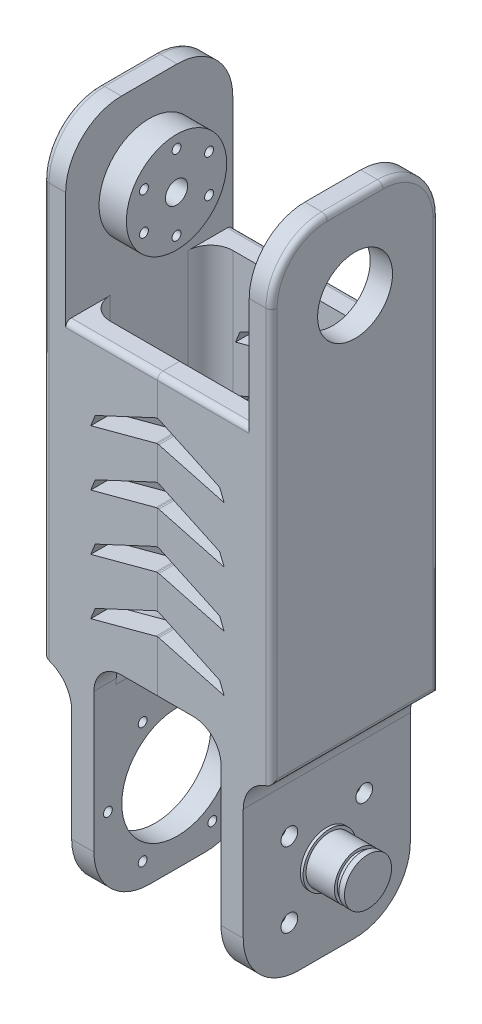
SolidWorks part; units mm, degrees
other "标注1"
sketch "草图21" plane through (0, -160, -30) normal (-0.4801, -0.1175, -0.8693) x (-0.746, 0.5761, 0.3342)
ref_plane "前视基准面" through (0, 0, 0) normal (0, 0, 1) x (1, 0, 0)
ref_plane "上视基准面" through (0, 0, 0) normal (0, 1, 0) x (1, 0, 0)
ref_plane "右视基准面" through (0, 0, 0) normal (1, 0, 0) x (0, 0, -1)
other "Configuration Table"
sketch "草图1" plane through (0, 0, 0) normal (1, 0, 0) x (0, 0, -1)
  line L1 (30, -80) -> (-30, -80)
  line L2 (30, -80) -> (30, 80)
  line L3 (30, 80) -> (-30, 80)
  line L4 (-30, -80) -> (-30, 80)
  line L5 (30, -80) -> (-30, 80) construction
  line L6 (30, 80) -> (-30, -80) construction
  point P0 (0, 0)
  dimension "D1" = 160
  dimension "D2" = 60
extrude "凸台-拉伸1" add sketch "草图1" along normal blind 8
sketch "草图2" plane through (8, 0, 0) normal (1, 0, 0) x (0, 0, -1)
  line L1 (30, 80) -> (-30, 80) construction
  circle A0 centre (0, 50) radius 13.5 construction
  circle A2 centre (0, 63.5) radius 1.6
  circle A4 centre (11.6913, 56.75) radius 1.6
  circle A5 centre (11.6913, 43.25) radius 1.6
  circle A6 centre (0, 36.5) radius 1.6
  circle A7 centre (-11.6913, 43.25) radius 1.6
  circle A8 centre (-11.6913, 56.75) radius 1.6
  circle A12 centre (0, 50) radius 4
  point P6 (0, 80)
  point P26 (0, 50)
  dimension "D3" = 27
  dimension "D7" = 3.2
  dimension "D11" = 8
  dimension "D2" = 30
  dimension "D9" = 6
extrude "切除-拉伸1" cut sketch "草图2" against normal through all
sketch "草图20" plane through (8, 0, 0) normal (1, 0, 0) x (0, 0, -1)
  circle A0 centre (0, 50) radius 18
  dimension "D1" = 36
extrude "凸台-拉伸7" add sketch "草图20" along normal blind 9.8
sketch "草图3" plane through (8, 0, 0) normal (1, 0, 0) x (0, 0, -1)
  line L0 (-30, 80) -> (-30, -80) construction
  line L1 (-22, -80) -> (-30, -80)
  line L2 (-22, -80) -> (-22, 20)
  line L3 (-22, 20) -> (-30, 20)
  line L4 (-30, -80) -> (-30, 20)
  line L5 (-22, -80) -> (-30, 20) construction
  line L6 (-22, 20) -> (-30, -80) construction
  line L7 (30, -80) -> (22, -80)
  line L8 (30, -80) -> (30, 20)
  line L9 (30, 20) -> (22, 20)
  line L10 (22, -80) -> (22, 20)
  line L11 (30, -80) -> (22, 20) construction
  line L12 (30, 20) -> (22, -80) construction
  line L13 (30, -80) -> (30, 80) construction
  line L14 (30, 80) -> (-30, 80) construction
  line L16 (-30, -80) -> (30, -80) construction
  point P0 (-26, -30)
  point P5 (26, -30)
  dimension "D1" = 60
  dimension "D3" = 60
  dimension "D5" = 8
  dimension "D6" = 8
extrude "凸台-拉伸2" add sketch "草图3" along normal blind 65.9
sketch "草图4" plane through (73.9, 0, 0) normal (1, 0, 0) x (0, 0, -1)
  line L0 (30, -80) -> (-30, 80) construction
  line L1 (30, -80) -> (-30, -80)
  line L2 (30, -80) -> (30, 80)
  line L3 (30, 80) -> (-30, 80)
  line L4 (-30, -80) -> (-30, 80)
  line L5 (30, -80) -> (-30, 80) construction
  line L6 (30, 80) -> (-30, -80) construction
  line L7 (30, 80) -> (-30, 80) construction
  point P0 (0, 0)
extrude "凸台-拉伸3" add sketch "草图4" along normal blind 8
sketch "草图9" plane through (73.9, 0, 0) normal (-1, 0, 0) x (0, 0, 1)
  circle A0 centre (0, 50) radius 13.45
  dimension "D1" = 26.9
extrude "切除-拉伸5" cut sketch "草图9" against normal up to next
sketch "草图11" plane through (0, 0, 30) normal (0, 0, 1) x (1, 0, 0)
  line L0 (0, 80) -> (0, -80) construction
  line L1 (0, -80) -> (18.15, -80)
  line L2 (0, -80) -> (0, -88)
  line L3 (0, -88) -> (18.15, -88)
  line L4 (18.15, -80) -> (18.15, -88)
  line L5 (81.9, -80) -> (63.75, -80)
  line L6 (81.9, -80) -> (81.9, -88)
  line L7 (81.9, -88) -> (63.75, -88)
  line L8 (63.75, -80) -> (63.75, -88)
  line L9 (81.9, 80) -> (81.9, -80) construction
  line L11 (18.15, -88) -> (10.15, -88)
  line L12 (18.15, -88) -> (18.15, -160)
  line L13 (18.15, -160) -> (10.15, -160)
  line L14 (10.15, -88) -> (10.15, -160)
  line L15 (63.75, -88) -> (71.75, -88)
  line L16 (63.75, -88) -> (63.75, -160)
  line L17 (63.75, -160) -> (71.75, -160)
  line L18 (71.75, -88) -> (71.75, -160)
  line M10 (0, -80) -> (81.9, -80)
  dimension "D1" = 8
  dimension "D2" = 8
  dimension "D3" = 45.6
  dimension "D4" = 72
  dimension "D5" = 72
  dimension "D6" = 8
  dimension "D7" = 8
extrude "凸台-拉伸4" add sketch "草图11" against normal blind 60 contours L3 L14 L13 L12 | L4 L2 L3 M10 | L8 L7 L6 M10 | L18 L7 L16 L17 region at (72.825, -84, 30) region at (9.075, -84, 30) region at (14.15, -124, 30) region at (67.75, -124, 30)
fillet "圆角1" radius 20 8 edges at (4, 80, -30) (4, 80, 30) (77.9, 80, -30) (77.9, 80, 30) (67.75, -160, -30) (67.75, -160, 30) (14.15, -160, -30) (14.15, -160, 30)
fillet "圆角2" radius 12 4 edges at (63.75, -80, 0) (18.15, -80, 0) (71.75, -88, 0) (10.15, -88, 0)
sketch "草图13" plane through (71.75, 0, 0) normal (1, 0, 0) x (0, 0, -1)
  line L0 (10, -160) -> (-10, -160) construction
  line L1 (0, -130) -> (13.435, -116.565) construction
  line L3 (0, -130) -> (0, -111) construction
  circle A0 centre (0, -130) radius 19 construction
  circle A1 centre (13.435, -116.565) radius 1.6
  circle A2 centre (13.435, -143.435) radius 1.6
  circle A3 centre (-13.435, -143.435) radius 1.6
  circle A4 centre (-13.435, -116.565) radius 1.6
  point P4 (0, -160)
  point P5 (0.0241, -160.1066)
  point P17 (0, -130)
  dimension "D1" = 38
  dimension "D3" = 3.2
  dimension "D2" = 30
  dimension "D5" = 45
  dimension "D4" = 4
extrude "切除-拉伸6" cut sketch "草图13" against normal up to next
sketch "草图12" plane through (10.15, 0, 0) normal (-1, 0, 0) x (0, 0, 1)
  circle A0 centre (0, -130) radius 25 construction
  circle A1 centre (-12.5, -108.3494) radius 1.6
  circle A2 centre (12.5, -108.3494) radius 1.6
  circle A3 centre (25, -130) radius 1.6
  circle A4 centre (12.5, -151.6506) radius 1.6
  circle A5 centre (-12.5, -151.6506) radius 1.6
  circle A6 centre (-25, -130) radius 1.6
  circle A7 centre (0, -130) radius 20
  point P2 (0, 0)
  point P17 (0, -130)
  dimension "D1" = 50
  dimension "D2" = 3.2
  dimension "D4" = 40
  dimension "D3" = 6
sketch "草图14" plane through (71.75, 0, 0) normal (1, 0, 0) x (0, 0, -1)
  circle A0 centre (0, -130) radius 8.45
  dimension "D1" = 16.9
extrude "凸台-拉伸5" add sketch "草图14" along normal blind 14.8
ref_plane "基准面1" through (84.55, 0, 0) normal (1, 0, 0) x (0, 0, -1)
sketch "草图15" plane through (84.55, 0, 0) normal (1, 0, 0) x (0, 0, -1)
  circle A0 centre (0, -130) radius 8.45
  circle A1 centre (0, -130) radius 7.45
  dimension "D1" = 16.9
  dimension "D2" = 14.9
extrude "切除-拉伸7" cut sketch "草图15" against normal blind 1.6
extrude "切除-拉伸8" cut sketch "草图12" against normal up to next
sketch "草图16" plane through (0, 0, 0) normal (-1, 0, 0) x (0, 0, 1)
  circle A0 centre (0, 63.5) radius 3
  circle A1 centre (11.6913, 56.75) radius 3
  circle A2 centre (11.6913, 43.25) radius 3
  circle A3 centre (0, 36.5) radius 3
  circle A4 centre (-11.6913, 43.25) radius 3
  circle A5 centre (-11.6913, 56.75) radius 3
  point P17 (0, 50)
  dimension "D1" = 6
  dimension "D2" = 6
extrude "切除-拉伸9" cut sketch "草图16" against normal blind 4
sketch "草图17" plane through (10.15, 0, 0) normal (-1, 0, 0) x (0, 0, 1)
  circle A0 centre (-12.5, -108.3494) radius 3
  circle A1 centre (12.5, -108.3494) radius 3
  circle A2 centre (25, -130) radius 3
  circle A3 centre (12.5, -151.6506) radius 3
  circle A4 centre (-12.5, -151.6506) radius 3
  circle A5 centre (-25, -130) radius 3
  point P15 (0, -130)
  dimension "D1" = 6
  dimension "D2" = 6
extrude "切除-拉伸10" cut sketch "草图17" against normal blind 4
sketch "草图18" plane through (71.75, 0, 0) normal (1, 0, 0) x (0, 0, -1)
  circle A0 centre (13.435, -116.565) radius 3
  circle A1 centre (13.435, -143.435) radius 3
  circle A2 centre (-13.435, -143.435) radius 3
  circle A3 centre (-13.435, -116.565) radius 3
  point P12 (0, -130)
  dimension "D1" = 6
  dimension "D2" = 4
extrude "切除-拉伸11" cut sketch "草图18" against normal blind 4
sketch "草图19" plane through (71.75, 0, 0) normal (1, 0, 0) x (0, 0, -1)
  circle A0 centre (0, -130) radius 9.5
  dimension "D1" = 19
extrude "凸台-拉伸6" add sketch "草图19" along normal blind 1
extrude "切除-拉伸12" cut sketch "草图2<3>" along normal up to next
sketch "草图2<3>" plane through (8, 0, 0) normal (1, 0, 0) x (0, 0, -1) same geometry as "草图2"
fillet "圆角3" radius 8 4 edges at (8, -30, -22) (8, -30, 22) (73.9, -30, 22) (73.9, -30, -22)
fillet "圆角4" radius 2 14 edges at (81.9, -14, 30) (81.9, 74.1421, 24.1421) (81.9, 80, 0) (81.9, 74.1421, -24.1421) (81.9, -14, -30) (0, -14, 30) (0, 74.1421, 24.1421) (0, 80, 0) (0, 74.1421, -24.1421) (81.9, -88, 0) (0, -88, 0) (40.95, 20, 30) (40.95, 20, -30) (0, -14, -30)
fillet "圆角5" radius 10 2 edges at (18.15, -80, -26) (63.75, -80, -26)
ref_plane "基准面2" through (40.95, 0, 0) normal (1, 0, 0) x (0, 0, -1)
sketch "草图25" plane through (0, 0, -30) normal (0, 0, -1) x (-1, 0, 0)
  line L1 (-41.7952, -53.9768) -> (-63.2902, -64)
  line L7 (-40.95, 30.8) -> (-40.95, -30.8) construction
  line L8 (-63.2902, -64) -> (-64.9, -68)
  line L9 (-64.9, -68) -> (-41.4676, -61.7213)
  line L11 (-40.4324, -61.7213) -> (-17, -68)
  line L12 (-17, -68) -> (-18.6098, -64)
  line L13 (-18.6098, -64) -> (-40.1048, -53.9768)
  line L14 (-2, -88.4909) -> (-2, 60) construction
  line L15 (-53.75, -80) -> (-28.15, -80) construction
  arc A0 (-41.4676, -61.7213) -> (-40.4324, -61.7213) centre (-40.95, -63.6532) cw
  arc A1 (-41.7952, -53.9768) -> (-40.1048, -53.9768) centre (-40.95, -55.7894) cw
  point P4 (-40.95, -62.0106)
  point P9 (-13.7607, -69.5864)
  point P16 (-40.95, -61.5826)
  point P19 (-40.95, -53.5826)
  dimension "D7" = 2
  dimension "D2" = 8
  dimension "D1" = 4
  dimension "D3" = 65
  dimension "D4" = 65
  dimension "D5" = 12
  dimension "D6" = 15
  dimension "D8" = 150
extrude "切除-拉伸13" cut sketch "草图25" against normal through all
pattern_linear "阵列(线性)1" count 4 spacing 20 along (0, 1, 0) of "切除-拉伸13"
split "分割1" trim tools "基准面2" bodies to split 130 resulting bodies 127 128
